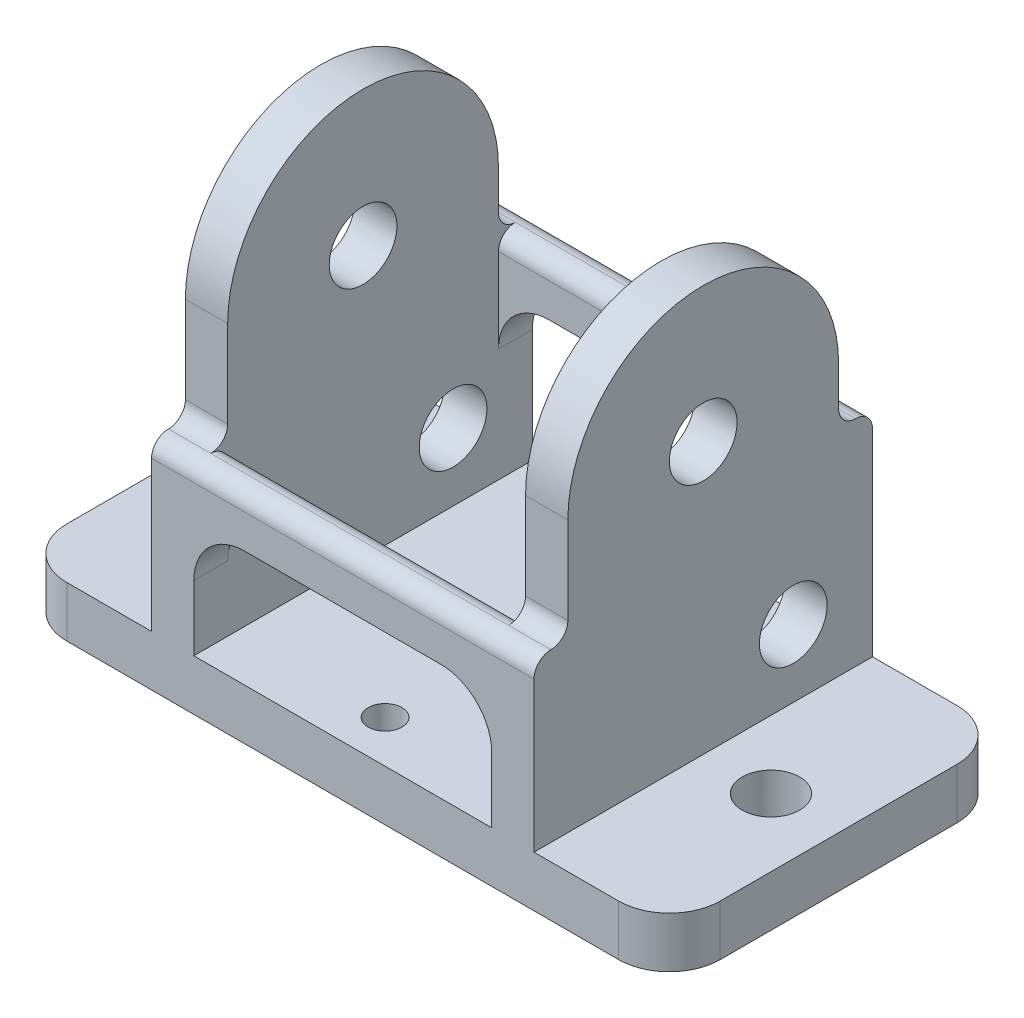
SolidWorks part; units mm, degrees
note: The reader was unsure of these and kept them because the rebuilt part matched: shared geometry of "Esquisse3<3>", "Esquisse3<5>".
ref_plane "Plan de face" through (0, 0, 0) normal (0, 0, 1) x (1, 0, 0)
ref_plane "Plan de dessus" through (0, 0, 0) normal (0, 1, 0) x (1, 0, 0)
ref_plane "Plan de droite" through (0, 0, 0) normal (1, 0, 0) x (0, 0, -1)
sketch "Esquisse2" plane through (0, 0, 0) normal (0, 0, 1) x (1, 0, 0)
  line L0 (0, 1.475) -> (0, -1.8592) construction
  line L1 (-2.1467, 0) -> (3.7613, 0) construction
  line L4 (8.8, 2) -> (11.3, 2)
  line L5 (11.3, 2) -> (11.3, 8)
  line L6 (11.3, 8) -> (8.8, 8)
  line L7 (8.8, 8) -> (8.8, 2)
  dimension "D1" = 2.5
  dimension "D2" = 2
  dimension "D5" = 8
  dimension "D6" = 8.8
revolve "Révolution1" add sketch "Esquisse2" angle 360 about L1
sketch "Esquisse3" plane through (11.3, 0, 0) normal (1, 0, 0) x (0, 0, -1)
  line L1 (-10, -19) -> (10, -19)
  line L3 (-10, -16) -> (10, -16)
  line L4 (3.318, 0) -> (3.318, -16) construction
  line L5 (8, 0) -> (8, -6.3137)
  line L6 (5.6569, -5.6569) -> (12.7279, 1.4142) construction
  line L7 (0, -8) -> (10, -8) construction
  line L8 (8, -3.3137) -> (10, -3.3137)
  line L9 (10, -3.3137) -> (10, -19)
  line L10 (8, -6.3137) -> (10, -6.3137)
  line L11 (-5.6569, -5.6569) -> (-12.7279, 1.4142) construction
  line L12 (-8, -6.1421) -> (-10, -6.1421)
  line L13 (-12.7279, -1.4142) -> (-6.1421, -8) construction
  line L14 (-8, 0) -> (-8, -9.1421)
  line L15 (-8, -9.1421) -> (-10, -9.1421)
  line L16 (-10, -6.1421) -> (-10, -19)
  circle A0 centre (0, 0) radius 8 construction
  arc A1 (-8, 0) -> (8, 0) centre (0, 0) ccw
  circle A2 centre (0, 0) radius 3.318 construction
  circle A3 centre (5.318, -12) radius 2
  dimension "D3" = 6.636
  dimension "D4" = 4
  dimension "D5" = 2
  dimension "D1" = 2
  dimension "D2" = 3
  dimension "D6" = 45
  dimension "D7" = 10
  dimension "D8" = 2
  dimension "D9" = 3
  dimension "D10" = 2
  dimension "D11" = 45
  dimension "D12" = 2
  dimension "D13" = 3
extrude "Boss.-Extru.1" add sketch "Esquisse3" against normal up to surface (2.5 mm away)
extrude "Boss.-Extru.2" add sketch "Esquisse3<3>" against normal up to surface (8.8 mm away) from surface at -2.5 up to plane "Plan de droite"
sketch "Esquisse3<3>" plane through (11.3, 0, 0) normal (1, 0, 0) x (0, 0, -1) same geometry as "Esquisse3"
extrude "Boss-Extrude1" add sketch "Esquisse3<5>" along normal blind 8 contours L3 L16 L1 L9
sketch "Esquisse3<5>" plane through (11.3, 0, 0) normal (1, 0, 0) x (0, 0, -1) same geometry as "Esquisse3"
sketch "Sketch4" plane through (0, -16, 0) normal (0, 1, 0) x (1, 0, 0)
  line L0 (19.3, 10) -> (11.3, 10) construction
  circle A0 centre (15.3, 0) radius 1.7
  point P6 (15.3, 10)
  dimension "D1" = 3.4
extrude "Cut-Extrude1" cut sketch "Sketch4" against normal up to next
mirror "Symétrie1" about plane through (0, 0, 0) normal (1, 0, 0) of bodies 110 103
hole_wizard "Trous de centrage Ø2.0mm1" positions "Sketch1" profile "Sketch3" hole size "Ø2.0" standard "Ansi Metric" end condition up to next
sketch "Sketch1" plane through (0, -16, 0) normal (0, 1, 0) x (1, 0, 0)
  point P3 (0, -7.5)
  dimension "D1" = 7.5
sketch "Sketch3" plane through (0, -16, 7.5) normal (1, 0, 0) x (0, 0, 1)
  line L0 (0, 0) -> (0, 3)
  line L1 (0, 3) -> (1, 3)
  line L2 (1, 3) -> (1, 0)
  line L5 (1, 0) -> (0, 0)
  line L11 (0, -6.35) -> (0, 107.95) construction
  dimension "Thru Hole Dia." = 2
  dimension "Thru Hole Depth" = 3
fillet "Fillet1" radius 1 4 edges at (-10.05, -3.3137, -8) (-10.05, -6.1421, 8) (10.05, -3.3137, -8) (10.05, -6.1421, 8)
fillet "Fillet2" radius 1 4 edges at (0, -3.3137, -8) (0, -3.3137, -10) (0, -6.1421, 10) (0, -6.1421, 8)
fillet "Fillet3" radius 3 8 edges at (-8.8, -6.3137, -9) (8.8, -6.3137, -9) (-8.8, -9.1421, 9) (8.8, -9.1421, 9) (-19.3, -17.5, -10) (-19.3, -17.5, 10) (19.3, -17.5, -10) (19.3, -17.5, 10)
